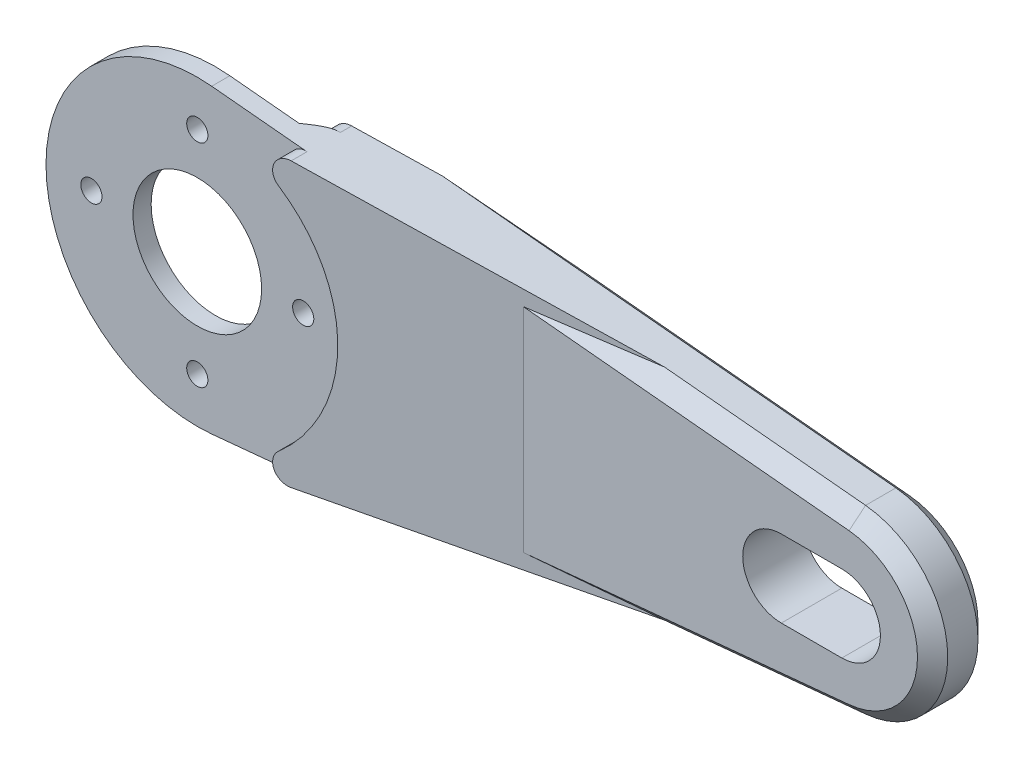
SolidWorks part; units mm, degrees
ref_plane "前视基准面" through (0, 0, 0) normal (0, 0, 1) x (1, 0, 0)
ref_plane "上视基准面" through (0, 0, 0) normal (0, 1, 0) x (1, 0, 0)
ref_plane "右视基准面" through (0, 0, 0) normal (1, 0, 0) x (0, 0, -1)
other "Configuration Table"
sketch "草图1" plane through (0, 0, 0) normal (0, 0, 1) x (1, 0, 0)
  line L0 (0, 0) -> (42, 0) construction
  line L3 (0.9524, 9.9545) -> (42.5714, 5.9727)
  line L4 (0.9524, -9.9545) -> (42.5714, -5.9727)
  arc A0 (0.9524, 9.9545) -> (0.9524, -9.9545) centre (0, 0) ccw
  arc A2 (42.5714, 5.9727) -> (42.5714, -5.9727) centre (42, 0) cw
  point P4 (32.5, -0.2057)
  dimension "D1" = 6
  dimension "D3" = 10
  dimension "D4" = 42
extrude "凸台-拉伸1" add sketch "草图1" along normal mid plane 8
sketch "草图3" plane through (0, 0, 4) normal (0, 0, 1) x (1, 0, 0)
  line L0 (0, 0) -> (88.1536, 0) construction
  line L1 (38, 0) -> (42, 0) construction
  line L2 (38, 2.55) -> (42, 2.55)
  line L3 (38, -2.55) -> (42, -2.55)
  arc A0 (38, 2.55) -> (38, -2.55) centre (38, 0) ccw
  arc A1 (42, -2.55) -> (42, 2.55) centre (42, 0) ccw
  point P6 (40, 0)
  dimension "D1" = 38
  dimension "D2" = 2.55
extrude "切除-拉伸1" cut sketch "草图3" against normal through all
sketch "草图5" plane through (0, 0, 4) normal (0, 0, 1) x (1, 0, 0)
  circle A0 centre (0, 0) radius 10
  dimension "D1" = 20
extrude "切除-拉伸2" cut sketch "草图5" against normal blind 3.4
mirror "镜向7" about plane through (0, 0, 0) normal (0, 0, 1) of "切除-拉伸2"
sketch "草图6" plane through (0, 0, 0.6) normal (0, 0, 1) x (1, 0, 0)
  line L0 (0, -7) -> (0, 7) construction
  line L1 (7, 0) -> (-7, 0) construction
  circle A0 centre (0, 7) radius 0.7
  circle A1 centre (0, -7) radius 0.7
  circle A2 centre (7, 0) radius 0.7
  circle A3 centre (-7, 0) radius 0.7
  dimension "D1" = 1.4
  dimension "D2" = 14
  dimension "D3" = 14
extrude "切除-拉伸3" cut sketch "草图6" against normal through all
sketch "草图8" plane through (0, 0, 0.6) normal (0, 0, 1) x (1, 0, 0)
  circle A0 centre (0, 0) radius 4.25
  dimension "D1" = 8.5
extrude "切除-拉伸5" cut sketch "草图8" against normal through all
sketch "草图10" plane through (0, 0, 0) normal (0, 1, 0) x (1, 0, 0)
  line L0 (0.9524, 1.6) -> (0.9524, 4)
  line L1 (0.9524, 4) -> (20.9524, 4)
  line L2 (42.5714, 4) -> (0.9524, 4) construction
  line L3 (20.9524, 4) -> (0.9524, 1.6)
  line L4 (0.9524, -2.4) -> (20.9524, 0)
  line L6 (20.9524, 0) -> (48, 0)
  line L7 (48, -4) -> (48, 4) construction
  line L8 (48, 0) -> (48, -4)
  line L9 (48, -4) -> (0.9524, -4)
  line L10 (0.9524, -4) -> (0.9524, -2.4)
  line L12 (0.9524, 4) -> (0.9524, 0.6) construction
  line L15 (4.25, 0.6) -> (-4.25, 0.6) construction
  point P2 (1.3399, -4)
  point P4 (0, 0)
  point P11 (0, 0)
  point P12 (1.6306, -3.25)
  point P21 (0.9524, 0.85)
  point P22 (0.9524, 1.6209)
  point P24 (0, 0)
  dimension "D1" = 4
  dimension "D2" = 20
  dimension "D3" = 1
  dimension "D4" = 20
extrude "切除-拉伸7" cut sketch "草图10" against normal through all both and the other way through all
fillet "圆角1" radius 1 4 edges at (0.9524, 9.9545, -1.1) (0.9524, -9.9545, -1.1) (0.9524, 9.9545, 1.5) (0.9524, -9.9545, 1.5)
chamfer "倒角1" distance 1 angle 45 6 edges at (31.7619, 7.0069, -4) (48, 0, -4) (31.7619, -7.0069, -4) (31.7619, 7.0069, 0) (48, 0, 0) (31.7619, -7.0069, 0)
chamfer "倒角3" distance 1 angle 45 3 edges at (6.2325, -8.7477, -0.6) (6.2325, 8.7477, -0.6) (10, 0, -0.6)
